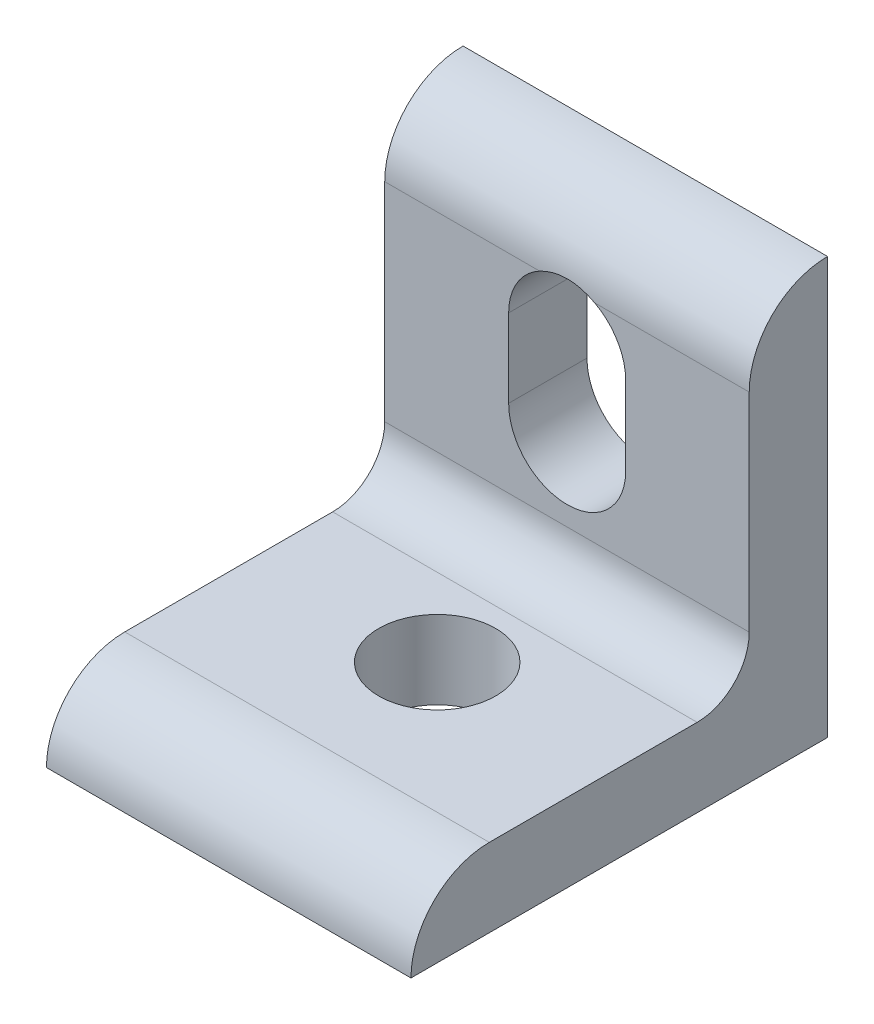
SolidWorks part; units mm, degrees
material "6061 Alloy"
ref_plane "Front Plane" through (0, 0, 0) normal (0, 0, 1) x (1, 0, 0)
ref_plane "Top Plane" through (0, 0, 0) normal (0, 1, 0) x (1, 0, 0)
ref_plane "Right Plane" through (0, 0, 0) normal (1, 0, 0) x (0, 0, -1)
sketch "Sketch1" plane through (0, 0, 0) normal (1, 0, 0) x (0, 0, -1)
  line L0 (6.2636, 22.5199) -> (-19.1364, 22.5199)
  line L1 (6.2636, 22.5199) -> (1.4884, 27.2951)
  line L2 (1.4884, 27.2951) -> (-14.3612, 27.2951)
  line L3 (6.2636, 27.2951) -> (-19.1364, 27.2951) construction
  arc A0 (-14.3612, 27.2951) -> (-19.1364, 22.5199) centre (-14.3612, 22.5199) ccw
  dimension "D1" = 4.7752
extrude "Extrude1" add sketch "Sketch1" along normal blind 22.225
sketch "Sketch2" plane through (0, 27.2951, 0) normal (0, 1, 0) x (1, 0, 0)
  circle A0 centre (11.1252, -6.4364) radius 3.5687
extrude "Cut-Extrude1" cut sketch "Sketch2" against normal through all
mirror "Mirror1" about plane through (22.225, 22.5199, -6.2636) normal (0, -0.7071, 0.7071) of bodies 102
fillet "Fillet1" radius 3.175 1 edges at (11.1125, 27.2951, -1.4884)
sketch "Sketch3" plane through (0, 0, -6.2636) normal (0, 0, -1) x (-1, 0, 0)
  line L2 (-14.6939, 39.9951) -> (-14.6939, 35.2199)
  line L4 (-7.5565, 39.9951) -> (-7.5565, 35.2199)
  line L6 (-14.6939, 35.2199) -> (-7.5565, 35.2199)
  arc A1 (-7.5565, 39.9951) -> (-14.6939, 39.9951) centre (-11.1252, 39.9951) ccw
  circle A3 centre (-11.1252, 35.2199) radius 3.5687 construction
extrude "Cut-Extrude2" cut sketch "Sketch3" against normal through all
